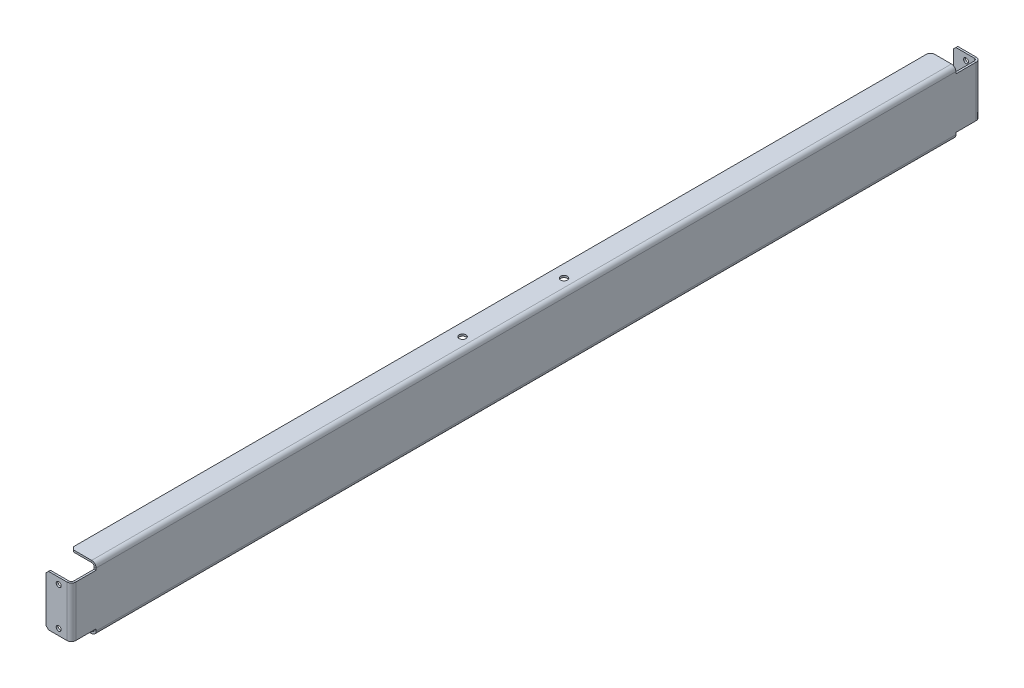
SolidWorks part; units mm, degrees
note: The reader was unsure of these and kept them because the rebuilt part matched: flange length of "Edge-Flange1", "Edge-Flange2".
material "Plain Carbon Steel"
ref_plane "Front Plane" through (0, 0, 0) normal (0, 0, 1) x (1, 0, 0)
ref_plane "Top Plane" through (0, 0, 0) normal (0, 1, 0) x (1, 0, 0)
ref_plane "Right Plane" through (0, 0, 0) normal (1, 0, 0) x (0, 0, -1)
sketch "Sketch1" plane through (0, 0, 0) normal (1, 0, 0) x (0, 0, -1)
  line L1 (-430.53, 0) -> (430.53, 0)
  line L2 (-430.53, 0) -> (-430.53, 63.5)
  line L3 (-430.53, 63.5) -> (430.53, 63.5)
  line L4 (430.53, 0) -> (430.53, 63.5)
  point P4 (0, 0)
  dimension "D1" = 861.06
  dimension "D2" = 63.5
base flange "Base-Flange1" sketch "Sketch1" thickness 1.8974 reverse thickness direction no parameters "D1"=2.54
edge flange "Edge-Flange1" sketch "Sketch10" flange profiles "Sketch10", "Sketch11" flange angle 90 flange length 25.4 flange position material inside bend radius 2.54 thickness 1.8974 relief rectangular parameters "D6"=10, "D8"=0.254
sketch "Sketch10" plane through (-1.8974, 63.5, 0) normal (0, -1, 0) x (0, 0, 1)
  line L2 (-430.53, 0) -> (-430.53, 23.5026)
  line L3 (-430.53, 23.5026) -> (430.53, 23.5026)
  line L4 (430.53, 23.5026) -> (430.53, 0)
  line L5 (430.53, 0) -> (-430.53, 0) construction
  line L6 (430.53, 0) -> (-430.53, 0)
sketch "Sketch11" plane through (-1.8974, 0, 0) normal (0, 1, 0) x (0, 0, -1)
  line L0 (430.53, 0) -> (-430.53, 0) construction
  line L1 (430.53, 0) -> (-430.53, 0)
  line L2 (430.53, 0) -> (430.53, 23.5026)
  line L3 (430.53, 23.5026) -> (-430.53, 23.5026)
  line L4 (-430.53, 23.5026) -> (-430.53, 0)
bend "EdgeBend1" bend radius 2.54 bend angle 90 parameters "D5"=1
bend "EdgeBend2" bend radius 2.54 bend angle 90 parameters "D5"=2
sketch "Sketch12" plane through (0, 0, 0) normal (1, 0, 0) x (0, 0, -1)
  line L0 (-430.53, 6.35) -> (-455.295, 6.35)
  line L1 (-430.53, 59.0626) -> (-430.53, 4.4374) construction
  line L2 (-455.295, 6.35) -> (-455.295, 57.15)
  line L7 (-455.295, 57.15) -> (-430.53, 57.15)
  line L8 (-430.53, 57.15) -> (-430.53, 6.35)
  point P9 (-430.53, 31.75)
  point P11 (-430.53, 31.75)
  dimension "D1" = 24.765
  dimension "D4" = 50.8
extrude "Boss-Extrude1" add sketch "Sketch12" against normal blind 1.8974
mirror "Mirror1" about plane through (0, 0, 0) normal (0, 0, 1) of "Boss-Extrude1"
sketch "Sketch13" plane through (0, 63.5, 0) normal (0, 1, 0) x (1, 0, 0)
  line L0 (-25.4, -430.53) -> (-25.4, 430.53) construction
  circle A0 centre (-12.7, 50.8) radius 3.3655
  circle A1 centre (-12.7, -50.8) radius 3.3655
  point P5 (-25.4, 0)
  dimension "D1" = 6.731
  dimension "D4" = 101.6
  dimension "D2" = 12.7
  dimension "D3" = 50.8
extrude "Cut-Extrude1" cut sketch "Sketch13" against normal through all normal cut yes
edge flange "Edge-Flange2" sketch "Sketch18" flange profiles "Sketch18", "Sketch19" flange angle 90 flange length 25.4 flange position material inside bend radius 2.54 thickness 1.8974 relief rectangular parameters "D6"=10, "D8"=0.254
sketch "Sketch18" plane through (-1.8974, 0, 455.295) normal (0, 0, 1) x (0, 1, 0)
  line L2 (6.35, 0) -> (6.35, 23.5026)
  line L3 (6.35, 23.5026) -> (57.15, 23.5026)
  line L4 (57.15, 23.5026) -> (57.15, 0)
  line L7 (57.15, 0) -> (6.35, 0) construction
  line L8 (57.15, 0) -> (6.35, 0)
sketch "Sketch19" plane through (-1.8974, 0, -455.295) normal (0, 0, -1) x (0, -1, 0)
  line L0 (-57.15, 0) -> (-6.35, 0) construction
  line L1 (-57.15, 0) -> (-6.35, 0)
  line L2 (-57.15, 0) -> (-57.15, 23.5026)
  line L3 (-57.15, 23.5026) -> (-6.35, 23.5026)
  line L4 (-6.35, 23.5026) -> (-6.35, 0)
bend "EdgeBend3" bend radius 2.54 bend angle 90 parameters "D5"=3
bend "EdgeBend4" bend radius 2.54 bend angle 90 parameters "D5"=4
sketch "Sketch20" plane through (0, 0, 455.295) normal (0, 0, 1) x (1, 0, 0)
  line L0 (0, 57.15) -> (0, 6.35) construction
  line L1 (-4.4374, 63.5) -> (-25.4, 63.5) construction
  circle A0 centre (-12.7, 50.8) radius 2.4638
  circle A1 centre (-12.7, 12.7) radius 2.4638
  dimension "D1" = 12.7
  dimension "D4" = 4.9276
  dimension "D2" = 12.7
  dimension "D3" = 38.1
extrude "Cut-Extrude2" cut sketch "Sketch20" against normal through all normal cut yes
chamfer "Chamfer1" distance 2.54 angle 45 8 edges at (-25.4, 62.5513, 430.53) (-25.4, 57.15, 454.3463) (-25.4, 6.35, 454.3463) (-25.4, 0.9487, 430.53) (-25.4, 0.9487, -430.53) (-25.4, 6.35, -454.3463) (-25.4, 62.5513, -430.53) (-25.4, 57.15, -454.3463)
sketch "Bend-Lines1" [suppressed] plane through (0, 0, 0) normal (0, 1, 0) x (1, 0, 0)
sketch "Bounding-Box1" [suppressed] plane through (0, 0, 0) normal (0, 1, 0) x (1, 0, 0)
sheet metal parameters "Sheet-Metal1" thickness 1.8974 parameters "D1"=2.54
flat pattern "Flat-Pattern1" [suppressed]
sketch "Bend-Lines2" plane through (0, 0, 0) normal (0, 1, 0) x (1, 0, 0)
sketch3d "Bounding-Box2" [suppressed]
  line L0 (-431.8, 0, 0) -> (431.8, 0, 0) construction
  line L1 (-431.8, 57.15, 0) -> (431.8, 57.15, 0) construction
  line L2 (-431.8, 0, 0) -> (-431.8, 57.15, 0) construction
  line L3 (431.8, 0, 0) -> (431.8, 57.15, 0) construction
sheet metal parameters "Sheet-Metal2" thickness 1.8974 parameters "D1"=2.54
flat pattern "Flat-Pattern1"
sketch "Bend-Lines2" plane through (0, 0, 0) normal (1, 0, 0) x (0, 0, -1)
  line L0 (-430.53, 1.6974) -> (430.53, 1.6974) construction
  line L1 (430.53, 55.4526) -> (-430.53, 55.4526) construction
  line L2 (-430.53, 1.6974) -> (430.53, 1.6974) construction
  line L3 (430.53, 55.4526) -> (-430.53, 55.4526) construction
sketch3d "Bounding-Box2" [suppressed]
  line L0 (430.53, -22.0053, 0) -> (-430.53, -22.0053, 0) construction
  line L1 (430.53, 79.1553, 0) -> (-430.53, 79.1553, 0) construction
  line L2 (430.53, -22.0053, 0) -> (430.53, 79.1553, 0) construction
  line L3 (-430.53, -22.0053, 0) -> (-430.53, 79.1553, 0) construction
bend of the flat pattern "Flatten-<EdgeBend1>1"
bend of the flat pattern "Flatten-<EdgeBend2>1"
sheet metal parameters "Sheet-Metal3" thickness 1.8974 parameters "D1"=2.54
flat pattern "Flat-Pattern1"
sketch "Bend-Lines2" plane through (0, 0, 0) normal (1, 0, 0) x (0, 0, -1)
  line L0 (-430.53, 1.6974) -> (430.53, 1.6974) construction
  line L1 (430.53, 55.4526) -> (-430.53, 55.4526) construction
  line L2 (-430.53, 1.6974) -> (430.53, 1.6974) construction
  line L3 (430.53, 55.4526) -> (-430.53, 55.4526) construction
sketch3d "Bounding-Box2" [suppressed]
  line L0 (430.53, -22.0053, 0) -> (-457.2, -22.0053, 0) construction
  line L1 (430.53, 79.1553, 0) -> (-457.2, 79.1553, 0) construction
  line L2 (430.53, -22.0053, 0) -> (430.53, 79.1553, 0) construction
  line L3 (-457.2, -22.0053, 0) -> (-457.2, 79.1553, 0) construction
bend of the flat pattern "Flatten-<EdgeBend1>1"
bend of the flat pattern "Flatten-<EdgeBend2>1"
sheet metal parameters "Sheet-Metal4" thickness 1.8974 parameters "D1"=2.54
flat pattern "Flat-Pattern1"
sketch "Bend-Lines2" plane through (0, 0, 0) normal (1, 0, 0) x (0, 0, -1)
  line L0 (-430.53, 1.6974) -> (430.53, 1.6974) construction
  line L1 (430.53, 55.4526) -> (-430.53, 55.4526) construction
  line L2 (-430.53, 1.6974) -> (430.53, 1.6974) construction
  line L3 (430.53, 55.4526) -> (-430.53, 55.4526) construction
sketch3d "Bounding-Box2" [suppressed]
  line L0 (457.2, -22.0053, 0) -> (-457.2, -22.0053, 0) construction
  line L1 (457.2, 79.1553, 0) -> (-457.2, 79.1553, 0) construction
  line L2 (457.2, -22.0053, 0) -> (457.2, 79.1553, 0) construction
  line L3 (-457.2, -22.0053, 0) -> (-457.2, 79.1553, 0) construction
bend of the flat pattern "Flatten-<EdgeBend1>1"
bend of the flat pattern "Flatten-<EdgeBend2>1"
sheet metal parameters "Sheet-Metal5" thickness 1.8974 parameters "D1"=2.54
flat pattern "Flat-Pattern1"
sketch "Bend-Lines2" plane through (0, 0, 0) normal (1, 0, 0) x (0, 0, -1)
  line L0 (-430.53, 1.6974) -> (430.53, 1.6974) construction
  line L1 (430.53, 61.8026) -> (-430.53, 61.8026) construction
  line L2 (-430.53, 1.6974) -> (430.53, 1.6974) construction
  line L3 (430.53, 61.8026) -> (-430.53, 61.8026) construction
sketch3d "Bounding-Box2" [suppressed]
  line L0 (455.295, -22.0053, 0) -> (-455.295, -22.0053, 0) construction
  line L1 (455.295, 85.5053, 0) -> (-455.295, 85.5053, 0) construction
  line L2 (455.295, -22.0053, 0) -> (455.295, 85.5053, 0) construction
  line L3 (-455.295, -22.0053, 0) -> (-455.295, 85.5053, 0) construction
bend of the flat pattern "Flatten-<EdgeBend1>1"
bend of the flat pattern "Flatten-<EdgeBend2>1"
sheet metal parameters "Sheet-Metal6" thickness 1.8974 parameters "D1"=2.54
flat pattern "Flat-Pattern1"
sketch "Bend-Lines2" plane through (0, 0, 0) normal (1, 0, 0) x (0, 0, -1)
  line L0 (-430.53, 1.6974) -> (430.53, 1.6974) construction
  line L1 (430.53, 61.8026) -> (-430.53, 61.8026) construction
  line L2 (-430.53, 1.6974) -> (430.53, 1.6974) construction
  line L3 (430.53, 61.8026) -> (-430.53, 61.8026) construction
  line L4 (453.5976, 6.35) -> (453.5976, 57.15) construction
  line L5 (-453.5976, 57.15) -> (-453.5976, 6.35) construction
  line L6 (453.5976, 6.35) -> (453.5976, 57.15) construction
  line L7 (-453.5976, 57.15) -> (-453.5976, 6.35) construction
sketch3d "Bounding-Box2" [suppressed]
  line L0 (477.3003, -22.0053, 0) -> (-477.3003, -22.0053, 0) construction
  line L1 (477.3003, 85.5053, 0) -> (-477.3003, 85.5053, 0) construction
  line L2 (477.3003, -22.0053, 0) -> (477.3003, 85.5053, 0) construction
  line L3 (-477.3003, -22.0053, 0) -> (-477.3003, 85.5053, 0) construction
bend of the flat pattern "Flatten-<EdgeBend1>1"
bend of the flat pattern "Flatten-<EdgeBend2>1"
bend of the flat pattern "Flatten-<EdgeBend3>1"
bend of the flat pattern "Flatten-<EdgeBend4>1"
sheet metal parameters "Sheet-Metal7" thickness 1.8974 parameters "D1"=2.54
flat pattern "Flat-Pattern1"
sketch "Bend-Lines2" plane through (0, 0, 0) normal (1, 0, 0) x (0, 0, -1)
  line L0 (-430.53, 1.6974) -> (430.53, 1.6974) construction
  line L1 (430.53, 61.8026) -> (-430.53, 61.8026) construction
  line L2 (-430.53, 1.6974) -> (430.53, 1.6974) construction
  line L3 (430.53, 61.8026) -> (-430.53, 61.8026) construction
  line L4 (453.5976, 6.35) -> (453.5976, 57.15) construction
  line L5 (-453.5976, 57.15) -> (-453.5976, 6.35) construction
  line L6 (453.5976, 6.35) -> (453.5976, 57.15) construction
  line L7 (-453.5976, 57.15) -> (-453.5976, 6.35) construction
sketch3d "Bounding-Box2" [suppressed]
  line L0 (477.3003, -22.0053, 0) -> (-477.3003, -22.0053, 0) construction
  line L1 (477.3003, 85.5053, 0) -> (-477.3003, 85.5053, 0) construction
  line L2 (477.3003, -22.0053, 0) -> (477.3003, 85.5053, 0) construction
  line L3 (-477.3003, -22.0053, 0) -> (-477.3003, 85.5053, 0) construction
bend of the flat pattern "Flatten-<EdgeBend1>1"
bend of the flat pattern "Flatten-<EdgeBend2>1"
bend of the flat pattern "Flatten-<EdgeBend3>1"
bend of the flat pattern "Flatten-<EdgeBend4>1"
